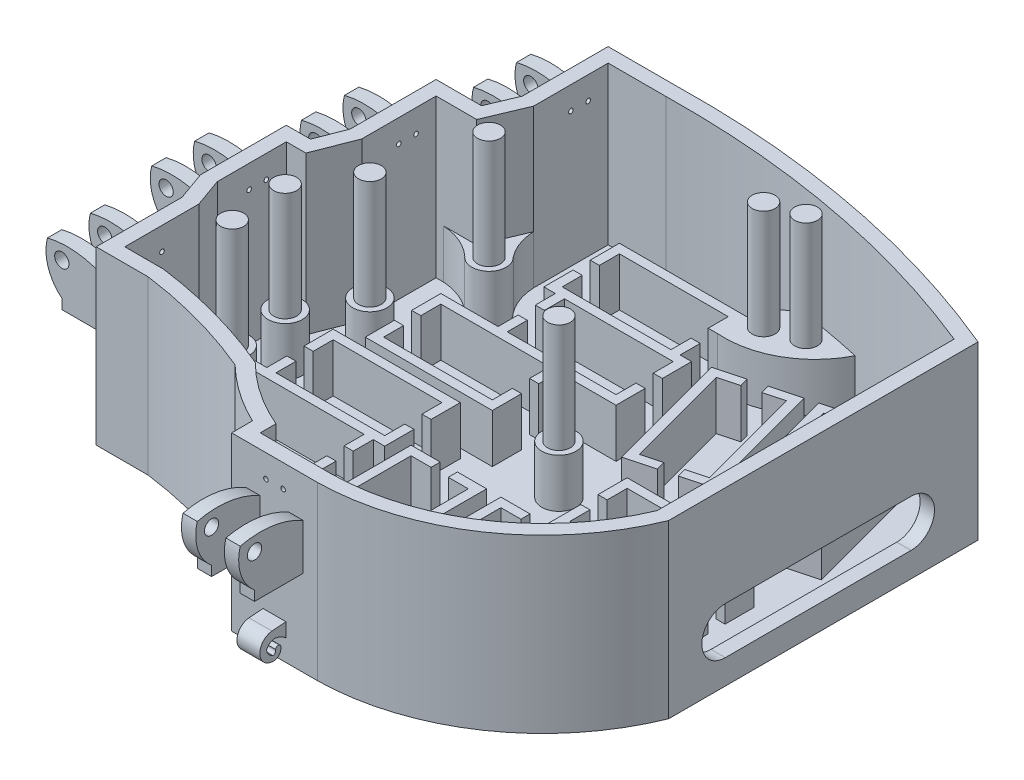
SolidWorks part; units mm, degrees
ref_plane "Front Plane" through (0, 0, 0) normal (0, 0, 1) x (1, 0, 0)
ref_plane "Top Plane" through (0, 0, 0) normal (0, 1, 0) x (1, 0, 0)
ref_plane "Right Plane" through (0, 0, 0) normal (1, 0, 0) x (0, 0, -1)
ref_plane "Palm Side Plane" through (0, 38.1, 0) normal (0, 1, 0) x (1, 0, 0)
ref_plane "Left Side Plane" through (0, 0, 63.5) normal (0, 0, 1) x (1, 0, 0)
ref_plane "Top Side Plane" through (-69.85, 0, 0) normal (1, 0, 0) x (0, 0, -1)
ref_plane "Wrist Plane" through (62.9138, 0, 0) normal (1, 0, 0) x (0, 0, -1)
sketch "Hand Direction Arrow" plane through (0, 38.1, 0) normal (0, 1, 0) x (1, 0, 0)
  line L0 (49.8191, -114.0829) -> (-36.738, -114.0829) construction
  line L1 (-36.738, -114.0829) -> (-22.4792, -131.555) construction
  line L2 (-36.738, -114.0829) -> (-22.4792, -99.8241) construction
sketch "Sketch2" plane through (0, 0, 0) normal (0, 1, 0) x (1, 0, 0)
  line L5 (-69.85, -63.5) -> (69.85, 63.5) construction
  line L6 (-69.85, 63.5) -> (69.85, -63.5) construction
  line L7 (-20.7784, 52.7587) -> (-36.189, 52.7587)
  line L8 (-36.189, 52.7587) -> (-36.189, 33.7087)
  line L9 (-42.9594, -42.4913) -> (-54.5039, -42.4913)
  line L10 (-54.5039, -42.4913) -> (-54.5039, -23.4413)
  line L11 (-54.5039, -23.4413) -> (-56.7676, -17.0913)
  line L12 (-51.4171, 1.9587) -> (-48.9477, 8.3087)
  line L14 (-56.7676, -17.0913) -> (-56.7676, 1.9587)
  line L15 (-56.7676, 1.9587) -> (-51.4171, 1.9587)
  line L16 (-38.8642, 27.3587) -> (-36.189, 33.7087)
  line L19 (15.3118, -63.2103) -> (-3.7382, -63.2103)
  line L20 (-3.7382, -63.2103) -> (-3.7382, -58.593)
  line L21 (61.5724, -31.5884) -> (61.5724, 37.0553)
  line L22 (-48.9477, 8.3087) -> (-48.9477, 27.3587)
  line L23 (-48.9477, 27.3587) -> (-38.8642, 27.3587)
  arc A0 (61.5724, 37.0553) -> (-20.7784, 52.7587) centre (-16.6219, -149.2259) ccw
  arc A2 (-42.9594, -42.4913) -> (-16.4221, -49.7553) centre (-56.8306, -145.2734) cw
  arc A5 (-3.7382, -58.593) -> (-16.4221, -49.7553) centre (16.7508, -15.6666) cw
  arc A6 (15.3118, -63.2103) -> (61.5724, -31.5884) centre (14.5642, -12.4678) ccw
  point P0 (0, 0)
  dimension "D1" = 19.05
  dimension "D2" = 19.05
  dimension "D3" = 19.05
  dimension "D4" = 19.05
  dimension "D5" = 19.05
  dimension "D6" = 6.35
  dimension "D7" = 6.35
extrude "Boss-Extrude1" add sketch "Sketch2" along normal blind 38.1
sketch "Sketch3" plane through (0, 38.1, 0) normal (0, 1, 0) x (1, 0, 0)
  line L5 (-68.58, -62.23) -> (68.58, 62.23) construction
  line L6 (-68.58, 62.23) -> (68.58, -62.23) construction
  line L7 (-20.1593, 49.595) -> (-33.014, 49.595)
  line L8 (-33.014, 49.595) -> (-33.014, 33.0672)
  line L10 (-36.189, 52.7587) -> (-36.189, 33.7087) construction
  line L11 (-54.5039, -23.4413) -> (-54.5039, -42.4913) construction
  line L12 (-42.7477, -39.3163) -> (-51.3289, -39.3163)
  line L13 (-51.3289, -39.3163) -> (-51.3289, -22.8923)
  line L18 (-53.5926, -16.5423) -> (-53.5926, -1.2163)
  line L19 (-53.5926, -1.2163) -> (-49.2452, -1.2163)
  line L22 (-56.7676, 1.9587) -> (-56.7676, -17.0913) construction
  line L23 (-51.4171, 1.9587) -> (-56.7676, 1.9587) construction
  line L24 (-45.7727, 7.713) -> (-45.7727, 24.1837)
  line L25 (-45.7727, 24.1837) -> (-36.7565, 24.1837)
  line L26 (-48.9477, 27.3587) -> (-48.9477, 8.3087) construction
  line L27 (-38.8642, 27.3587) -> (-48.9477, 27.3587) construction
  line L28 (-36.7565, 24.1837) -> (-33.014, 33.0672)
  line L29 (-36.189, 33.7087) -> (-38.8642, 27.3587) construction
  line L30 (-49.2452, -1.2163) -> (-45.7727, 7.713)
  line L31 (-54.5039, -42.4913) -> (-42.9594, -42.4913) construction
  line L32 (-51.3289, -22.8923) -> (-53.5926, -16.5423)
  line L33 (-56.7676, -17.0913) -> (-54.5039, -23.4413) construction
  line L34 (-48.9477, 8.3087) -> (-51.4171, 1.9587) construction
  line L35 (15.3312, -60.0353) -> (-0.5632, -60.0353)
  line L36 (-0.5632, -60.0353) -> (-0.5632, -56.5413)
  line L37 (-3.7382, -58.593) -> (-3.7382, -63.2103) construction
  line L38 (-3.7382, -63.2103) -> (15.3118, -63.2103) construction
  line L39 (58.3974, -30.9587) -> (58.3974, 34.9326)
  line L40 (61.5724, -31.5884) -> (61.5724, 37.0553) construction
  arc A1 (-20.1593, 49.595) -> (58.3974, 34.9326) centre (-16.6219, -149.2259) cw
  arc A4 (61.5724, 37.0553) -> (-20.7784, 52.7587) centre (-16.6219, -149.2259) ccw construction
  arc A5 (15.3118, -63.2103) -> (61.5724, -31.5884) centre (14.5642, -12.4678) ccw construction
  arc A8 (-42.7477, -39.3163) -> (-14.6223, -47.0711) centre (-56.8306, -145.2734) cw
  arc A9 (-16.4221, -49.7553) -> (-42.9594, -42.4913) centre (-56.8306, -145.2734) ccw construction
  arc A12 (15.3312, -60.0353) -> (58.3974, -30.9587) centre (14.5642, -12.4678) ccw
  arc A13 (-0.5632, -56.5413) -> (-14.6223, -47.0711) centre (16.7508, -15.6666) cw
  arc A14 (-16.4221, -49.7553) -> (-3.7382, -58.593) centre (16.7508, -15.6666) ccw construction
  point P0 (0, 0)
  point P6 (-45.5127, -25.7954)
  point P29 (-45.5127, -25.7954)
  point P52 (-54.0923, 1.9587)
  dimension "D2" = 3.175
  dimension "D3" = 3.175
  dimension "D5" = 3.175
  dimension "D6" = 3.175
  dimension "D8" = 3.175
  dimension "D4" = 3.175
  dimension "D7" = 3.175
  dimension "D9" = 3.175
  dimension "D10" = 3.175
  dimension "D11" = 3.175
  dimension "D12" = 3.175
  dimension "D13" = 3.175
  dimension "D14" = 3.175
  dimension "D15" = 3.175
  dimension "D16" = 3.175
  dimension "D17" = 3.175
extrude "Cut-Extrude1" cut sketch "Sketch3" against normal blind 34.925
sketch "Sketch6" plane through (0, 0, 0) normal (0, 1, 0) x (1, 0, 0)
  line L0 (-39.0579, -32.9145) -> (-37.0259, -32.9145)
  line L5 (-63.3937, -68.1577) -> (73.7663, 56.3023) construction
  line L6 (-64.5742, 57.9506) -> (72.5858, -66.5094) construction
  line L7 (-12.8959, -37.3595) -> (-37.0259, -37.3595)
  line L8 (-12.8959, -37.3595) -> (-12.8959, -32.9145)
  line L9 (-12.8959, -24.6595) -> (-37.0259, -24.6595)
  line L10 (-37.0259, -37.3595) -> (-37.0259, -32.9145)
  line L11 (-12.8959, -37.3595) -> (-37.0259, -24.6595) construction
  line L12 (-12.8959, -24.6595) -> (-37.0259, -37.3595) construction
  line L13 (-10.8639, -39.3915) -> (-39.0579, -39.3915)
  line L14 (-10.8639, -39.3915) -> (-10.8639, -32.9145)
  line L15 (-10.8639, -22.6275) -> (-39.0579, -22.6275)
  line L16 (-39.0579, -39.3915) -> (-39.0579, -32.9145)
  line L17 (-10.8639, -39.3915) -> (-39.0579, -22.6275) construction
  line L18 (-10.8639, -22.6275) -> (-39.0579, -39.3915) construction
  line L19 (-39.0579, -29.1045) -> (-37.0259, -29.1045)
  line L20 (-39.0579, -29.1045) -> (-39.0579, -22.6275)
  line L21 (-37.0259, -29.1045) -> (-37.0259, -24.6595)
  line L22 (-12.8959, -32.9145) -> (-10.8639, -32.9145)
  line L23 (-12.8959, -29.1045) -> (-10.8639, -29.1045)
  line L24 (-12.8959, -29.1045) -> (-12.8959, -24.6595)
  line L25 (-10.8639, -29.1045) -> (-10.8639, -22.6275)
  point P0 (5.5042, -5.6391)
  point P6 (-24.9609, -31.0095)
  point P29 (-24.9609, -31.0095)
  dimension "D6" = 2.032
  dimension "D7" = 2.032
  dimension "D9" = 12.7
  dimension "D10" = 24.13
  dimension "D11" = 4.445
  dimension "D12" = 4.445
  dimension "D13" = 4.445
  dimension "D14" = 4.445
extrude "Servo Box 1" add sketch "Sketch6" along normal blind 13.97
sketch "Sketch7" plane through (0, 0, 0) normal (0, 1, 0) x (1, 0, 0)
  line L0 (-36.5179, -18.1825) -> (-34.4859, -18.1825)
  line L5 (-10.8639, -22.6275) -> (-39.0579, -22.6275) construction
  line L7 (-10.3559, -22.6275) -> (-34.4859, -22.6275)
  line L8 (-10.3559, -22.6275) -> (-10.3559, -18.1825)
  line L9 (-10.3559, -9.9275) -> (-34.4859, -9.9275)
  line L10 (-34.4859, -22.6275) -> (-34.4859, -18.1825)
  line L11 (-10.3559, -22.6275) -> (-34.4859, -9.9275) construction
  line L12 (-10.3559, -9.9275) -> (-34.4859, -22.6275) construction
  line L13 (-8.3239, -24.6595) -> (-36.5179, -24.6595)
  line L14 (-8.3239, -24.6595) -> (-8.3239, -18.1825)
  line L15 (-8.3239, -7.8955) -> (-36.5179, -7.8955)
  line L16 (-36.5179, -24.6595) -> (-36.5179, -18.1825)
  line L17 (-8.3239, -24.6595) -> (-36.5179, -7.8955) construction
  line L18 (-8.3239, -7.8955) -> (-36.5179, -24.6595) construction
  line L19 (-36.5179, -14.3725) -> (-34.4859, -14.3725)
  line L20 (-36.5179, -14.3725) -> (-36.5179, -7.8955)
  line L21 (-34.4859, -14.3725) -> (-34.4859, -9.9275)
  line L22 (-10.3559, -18.1825) -> (-8.3239, -18.1825)
  line L23 (-10.3559, -14.3725) -> (-8.3239, -14.3725)
  line L24 (-10.3559, -14.3725) -> (-10.3559, -9.9275)
  line L25 (-8.3239, -14.3725) -> (-8.3239, -7.8955)
  line L26 (-39.0579, -22.6275) -> (-39.0579, -29.1045) construction
  point P0 (-7.5753, -5.9494)
  point P6 (-22.4209, -16.2775)
  point P29 (-22.4209, -16.2775)
  dimension "D2" = 2.032
  dimension "D3" = 2.54
  dimension "D6" = 2.032
  dimension "D7" = 2.032
  dimension "D9" = 12.7
  dimension "D10" = 24.13
  dimension "D11" = 4.445
  dimension "D12" = 4.445
  dimension "D13" = 4.445
  dimension "D14" = 4.445
extrude "Servo Box 2" add sketch "Sketch7" along normal blind 13.97
sketch "Sketch15" plane through (0, 0, 0) normal (0, -1, 0) x (1, 0, 0)
  line L0 (-31.4379, -4.4235) -> (-29.4059, -4.4235)
  line L5 (-8.3239, 7.8955) -> (-36.5179, 7.8955) construction
  line L6 (-36.5179, 7.8955) -> (-36.5179, 14.3725) construction
  line L7 (-5.2759, -8.8685) -> (-29.4059, -8.8685)
  line L8 (-5.2759, -8.8685) -> (-5.2759, -4.4235)
  line L9 (-5.2759, 3.8315) -> (-29.4059, 3.8315)
  line L10 (-29.4059, -8.8685) -> (-29.4059, -4.4235)
  line L11 (-5.2759, -8.8685) -> (-29.4059, 3.8315) construction
  line L12 (-5.2759, 3.8315) -> (-29.4059, -8.8685) construction
  line L13 (-3.2439, -10.9005) -> (-31.4379, -10.9005)
  line L14 (-3.2439, -10.9005) -> (-3.2439, -4.4235)
  line L15 (-3.2439, 5.8635) -> (-31.4379, 5.8635)
  line L16 (-31.4379, -10.9005) -> (-31.4379, -4.4235)
  line L17 (-3.2439, -10.9005) -> (-31.4379, 5.8635) construction
  line L18 (-3.2439, 5.8635) -> (-31.4379, -10.9005) construction
  line L19 (-31.4379, -0.6135) -> (-29.4059, -0.6135)
  line L20 (-31.4379, -0.6135) -> (-31.4379, 5.8635)
  line L21 (-29.4059, -0.6135) -> (-29.4059, 3.8315)
  line L22 (-5.2759, -4.4235) -> (-3.2439, -4.4235)
  line L23 (-5.2759, -0.6135) -> (-3.2439, -0.6135)
  line L24 (-5.2759, -0.6135) -> (-5.2759, 3.8315)
  line L25 (-3.2439, -0.6135) -> (-3.2439, 5.8635)
  point P0 (-6.5637, 8.998)
  point P6 (-17.3409, -2.5185)
  point P29 (-17.3409, -2.5185)
  dimension "D2" = 2.032
  dimension "D3" = 5.08
  dimension "D6" = 2.032
  dimension "D7" = 2.032
  dimension "D9" = 12.7
  dimension "D10" = 24.13
  dimension "D11" = 4.445
  dimension "D12" = 4.445
  dimension "D13" = 4.445
  dimension "D14" = 4.445
extrude "Servo Box 3" add sketch "Sketch15" against normal blind 13.97
sketch "Sketch16" plane through (0, 0, 0) normal (0, -1, 0) x (1, 0, 0)
  line L0 (-18.7379, -19.1555) -> (-16.7059, -19.1555)
  line L5 (-31.4379, -10.9005) -> (-3.2439, -10.9005) construction
  line L6 (-31.4379, -4.4235) -> (-31.4379, -10.9005) construction
  line L7 (7.4241, -23.6005) -> (-16.7059, -23.6005)
  line L8 (7.4241, -23.6005) -> (7.4241, -19.1555)
  line L9 (7.4241, -10.9005) -> (-16.7059, -10.9005)
  line L10 (-16.7059, -23.6005) -> (-16.7059, -19.1555)
  line L11 (7.4241, -23.6005) -> (-16.7059, -10.9005) construction
  line L12 (7.4241, -10.9005) -> (-16.7059, -23.6005) construction
  line L13 (9.4561, -25.6325) -> (-18.7379, -25.6325)
  line L14 (9.4561, -25.6325) -> (9.4561, -19.1555)
  line L15 (9.4561, -8.8685) -> (-18.7379, -8.8685)
  line L16 (-18.7379, -25.6325) -> (-18.7379, -19.1555)
  line L17 (9.4561, -25.6325) -> (-18.7379, -8.8685) construction
  line L18 (9.4561, -8.8685) -> (-18.7379, -25.6325) construction
  line L19 (-18.7379, -15.3455) -> (-16.7059, -15.3455)
  line L20 (-18.7379, -15.3455) -> (-18.7379, -8.8685)
  line L21 (-16.7059, -15.3455) -> (-16.7059, -10.9005)
  line L22 (7.4241, -19.1555) -> (9.4561, -19.1555)
  line L23 (7.4241, -15.3455) -> (9.4561, -15.3455)
  line L24 (7.4241, -15.3455) -> (7.4241, -10.9005)
  line L25 (9.4561, -15.3455) -> (9.4561, -8.8685)
  point P0 (1.9027, -6.9539)
  point P6 (-4.6409, -17.2505)
  point P29 (-4.6409, -17.2505)
  dimension "D2" = 2.032
  dimension "D3" = 12.7
  dimension "D6" = 2.032
  dimension "D7" = 2.032
  dimension "D9" = 12.7
  dimension "D10" = 24.13
  dimension "D11" = 4.445
  dimension "D12" = 4.445
  dimension "D13" = 4.445
  dimension "D14" = 4.445
extrude "Servo Box 4" add sketch "Sketch16" against normal blind 13.97
sketch "Sketch17" plane through (0, 0, 0) normal (0, -1, 0) x (1, 0, 0)
  line L0 (-21.2779, -33.8875) -> (-19.2459, -33.8875)
  line L5 (-18.7379, -25.6325) -> (9.4561, -25.6325) construction
  line L6 (-18.7379, -19.1555) -> (-18.7379, -25.6325) construction
  line L7 (4.8841, -38.3325) -> (-19.2459, -38.3325)
  line L8 (4.8841, -38.3325) -> (4.8841, -33.8875)
  line L9 (4.8841, -25.6325) -> (-19.2459, -25.6325)
  line L10 (-19.2459, -38.3325) -> (-19.2459, -33.8875)
  line L11 (4.8841, -38.3325) -> (-19.2459, -25.6325) construction
  line L12 (4.8841, -25.6325) -> (-19.2459, -38.3325) construction
  line L13 (6.9161, -40.3645) -> (-21.2779, -40.3645)
  line L14 (6.9161, -40.3645) -> (6.9161, -33.8875)
  line L15 (6.9161, -23.6005) -> (-21.2779, -23.6005)
  line L16 (-21.2779, -40.3645) -> (-21.2779, -33.8875)
  line L17 (6.9161, -40.3645) -> (-21.2779, -23.6005) construction
  line L18 (6.9161, -23.6005) -> (-21.2779, -40.3645) construction
  line L19 (-21.2779, -30.0775) -> (-19.2459, -30.0775)
  line L20 (-21.2779, -30.0775) -> (-21.2779, -23.6005)
  line L21 (-19.2459, -30.0775) -> (-19.2459, -25.6325)
  line L22 (4.8841, -33.8875) -> (6.9161, -33.8875)
  line L23 (4.8841, -30.0775) -> (6.9161, -30.0775)
  line L24 (4.8841, -30.0775) -> (4.8841, -25.6325)
  line L25 (6.9161, -30.0775) -> (6.9161, -23.6005)
  point P0 (6.1079, -24.4951)
  point P6 (-7.1809, -31.9825)
  point P29 (-7.1809, -31.9825)
  dimension "D2" = 2.032
  dimension "D3" = 2.54
  dimension "D6" = 2.032
  dimension "D7" = 2.032
  dimension "D9" = 12.7
  dimension "D10" = 24.13
  dimension "D11" = 4.445
  dimension "D12" = 4.445
  dimension "D13" = 4.445
  dimension "D14" = 4.445
extrude "Servo Box 5" add sketch "Sketch17" against normal blind 13.97
sketch "Sketch18" plane through (0, 0, 0) normal (0, -1, 0) x (1, 0, 0)
  line L0 (0.8802, 49.7413) -> (0.8802, 47.7093)
  line L7 (-3.5648, 23.5793) -> (-3.5648, 47.7093)
  line L8 (-3.5648, 23.5793) -> (0.8802, 23.5793)
  line L9 (9.1352, 23.5793) -> (9.1352, 47.7093)
  line L10 (-3.5648, 47.7093) -> (0.8802, 47.7093)
  line L11 (-3.5648, 23.5793) -> (9.1352, 47.7093) construction
  line L12 (9.1352, 23.5793) -> (-3.5648, 47.7093) construction
  line L13 (-5.5968, 21.5473) -> (-5.5968, 49.7413)
  line L14 (-5.5968, 21.5473) -> (0.8802, 21.5473)
  line L15 (11.1672, 21.5473) -> (11.1672, 49.7413)
  line L16 (-5.5968, 49.7413) -> (0.8802, 49.7413)
  line L17 (-5.5968, 21.5473) -> (11.1672, 49.7413) construction
  line L18 (11.1672, 21.5473) -> (-5.5968, 49.7413) construction
  line L19 (4.6902, 49.7413) -> (4.6902, 47.7093)
  line L20 (4.6902, 49.7413) -> (11.1672, 49.7413)
  line L21 (4.6902, 47.7093) -> (9.1352, 47.7093)
  line L22 (0.8802, 23.5793) -> (0.8802, 21.5473)
  line L23 (4.6902, 23.5793) -> (4.6902, 21.5473)
  line L24 (4.6902, 23.5793) -> (9.1352, 23.5793)
  line L25 (4.6902, 21.5473) -> (11.1672, 21.5473)
  point P0 (12.6654, 20.4496)
  point P6 (2.7852, 35.6443)
  point P29 (2.7852, 35.6443)
  dimension "D6" = 2.032
  dimension "D7" = 2.032
  dimension "D9" = 12.7
  dimension "D10" = 24.13
  dimension "D11" = 4.445
  dimension "D12" = 4.445
  dimension "D13" = 4.445
  dimension "D14" = 4.445
extrude "Servo Box 6" add sketch "Sketch18" against normal blind 13.97
sketch "Sketch19" plane through (0, 0, 0) normal (0, -1, 0) x (1, 0, 0)
  line L0 (20.8192, 49.7413) -> (20.8192, 47.7093)
  line L6 (11.1672, 21.5473) -> (11.1672, 49.7413) construction
  line L7 (16.3742, 23.5793) -> (16.3742, 47.7093)
  line L8 (16.3742, 23.5793) -> (20.8192, 23.5793)
  line L9 (29.0742, 23.5793) -> (29.0742, 47.7093)
  line L10 (16.3742, 47.7093) -> (20.8192, 47.7093)
  line L13 (14.3422, 21.5473) -> (14.3422, 49.7413)
  line L14 (14.3422, 21.5473) -> (20.8192, 21.5473)
  line L15 (31.1062, 21.5473) -> (31.1062, 49.7413)
  line L16 (14.3422, 49.7413) -> (20.8192, 49.7413)
  line L19 (24.6292, 49.7413) -> (24.6292, 47.7093)
  line L20 (24.6292, 49.7413) -> (31.1062, 49.7413)
  line L21 (24.6292, 47.7093) -> (29.0742, 47.7093)
  line L22 (20.8192, 23.5793) -> (20.8192, 21.5473)
  line L23 (24.6292, 23.5793) -> (24.6292, 21.5473)
  line L24 (24.6292, 23.5793) -> (29.0742, 23.5793)
  line L25 (24.6292, 21.5473) -> (31.1062, 21.5473)
  line L26 (11.1672, 49.7413) -> (4.6902, 49.7413) construction
  point P5 (0, 0)
  dimension "D2" = 0
  dimension "D3" = 2.032
  dimension "D5" = 3.175
  dimension "D6" = 2.032
  dimension "D4" = 2.032
  dimension "D7" = 2.032
  dimension "D9" = 12.7
  dimension "D10" = 24.13
  dimension "D11" = 4.445
  dimension "D12" = 4.445
  dimension "D13" = 4.445
  dimension "D14" = 4.445
extrude "Servo Box 7" add sketch "Sketch19" against normal blind 13.97
sketch "Sketch20" plane through (0, 0, 0) normal (0, -1, 0) x (1, 0, 0)
  line L0 (24.6292, 10.3085) -> (26.6612, 10.3085)
  line L7 (50.7912, 5.8635) -> (26.6612, 5.8635)
  line L8 (50.7912, 5.8635) -> (50.7912, 10.3085)
  line L9 (50.7912, 18.5635) -> (26.6612, 18.5635)
  line L10 (26.6612, 5.8635) -> (26.6612, 10.3085)
  line L13 (52.8232, 3.8315) -> (24.6292, 3.8315)
  line L14 (52.8232, 3.8315) -> (52.8232, 10.3085)
  line L15 (52.8232, 20.5955) -> (24.6292, 20.5955)
  line L16 (24.6292, 3.8315) -> (24.6292, 10.3085)
  line L19 (24.6292, 14.1185) -> (26.6612, 14.1185)
  line L20 (24.6292, 14.1185) -> (24.6292, 20.5955)
  line L21 (26.6612, 14.1185) -> (26.6612, 18.5635)
  line L22 (50.7912, 10.3085) -> (52.8232, 10.3085)
  line L23 (50.7912, 14.1185) -> (52.8232, 14.1185)
  line L24 (50.7912, 14.1185) -> (50.7912, 18.5635)
  line L25 (52.8232, 14.1185) -> (52.8232, 20.5955)
  line L26 (-3.2439, 5.8635) -> (-31.4379, 5.8635) construction
  point P3 (0, 0)
  dimension "D2" = 0
  dimension "D3" = 2.032
  dimension "D6" = 2.032
  dimension "D4" = 2.032
  dimension "D7" = 2.032
  dimension "D9" = 12.7
  dimension "D10" = 24.13
  dimension "D11" = 4.445
  dimension "D12" = 4.445
  dimension "D13" = 4.445
  dimension "D14" = 4.445
extrude "Servo Box 8" add sketch "Sketch20" against normal blind 13.97
sketch "Sketch21" plane through (0, 0, 0) normal (0, -1, 0) x (1, 0, 0)
  line L0 (22.6768, -29.4265) -> (23.2027, -27.4637)
  line L7 (33.7416, -5.3064) -> (27.4963, -28.6142)
  line L8 (33.7416, -5.3064) -> (29.448, -4.1559)
  line L9 (21.4743, -2.0194) -> (15.229, -25.3272)
  line L10 (27.4963, -28.6142) -> (23.2027, -27.4637)
  line L11 (33.7416, -5.3064) -> (15.229, -25.3272) construction
  line L12 (21.4743, -2.0194) -> (27.4963, -28.6142) construction
  line L13 (36.2303, -3.8695) -> (28.9331, -31.1029)
  line L14 (36.2303, -3.8695) -> (29.974, -2.1932)
  line L15 (20.0375, 0.4693) -> (12.7403, -26.764)
  line L16 (28.9331, -31.1029) -> (22.6768, -29.4265)
  line L17 (36.2303, -3.8695) -> (12.7403, -26.764) construction
  line L18 (20.0375, 0.4693) -> (28.9331, -31.1029) construction
  line L19 (18.9966, -28.4404) -> (19.5225, -26.4776)
  line L20 (18.9966, -28.4404) -> (12.7403, -26.764)
  line L21 (19.5225, -26.4776) -> (15.229, -25.3272)
  line L22 (29.448, -4.1559) -> (29.974, -2.1932)
  line L23 (25.7679, -3.1698) -> (26.2938, -1.2071)
  line L24 (25.7679, -3.1698) -> (21.4743, -2.0194)
  line L25 (26.2938, -1.2071) -> (20.0375, 0.4693)
  point P0 (22.3862, -0.6336)
  point P6 (24.4853, -15.3168)
  point P29 (24.4853, -15.3168)
  dimension "D6" = 2.032
  dimension "D7" = 2.032
  dimension "D9" = 12.7
  dimension "D10" = 24.13
  dimension "D11" = 4.445
  dimension "D12" = 4.445
  dimension "D13" = 4.445
  dimension "D14" = 4.445
extrude "Servo Box 9" add sketch "Sketch21" against normal blind 13.97
sketch "Sketch22" plane through (0, 0, 0) normal (0, -1, 0) x (1, 0, 0)
  line L0 (41.4457, -34.4556) -> (41.9716, -32.4928)
  line L7 (52.5105, -10.3355) -> (46.2652, -33.6433)
  line L8 (52.5105, -10.3355) -> (48.2169, -9.1851)
  line L9 (40.2432, -7.0485) -> (33.9979, -30.3563)
  line L10 (46.2652, -33.6433) -> (41.9716, -32.4928)
  line L11 (52.5105, -10.3355) -> (33.9979, -30.3563) construction
  line L12 (40.2432, -7.0485) -> (46.2652, -33.6433) construction
  line L13 (54.9992, -8.8987) -> (47.702, -36.132)
  line L14 (54.9992, -8.8987) -> (48.7429, -7.2223)
  line L15 (38.8064, -4.5598) -> (31.5092, -31.7931)
  line L16 (47.702, -36.132) -> (41.4457, -34.4556)
  line L17 (54.9992, -8.8987) -> (31.5092, -31.7931) construction
  line L18 (38.8064, -4.5598) -> (47.702, -36.132) construction
  line L19 (37.7655, -33.4695) -> (38.2915, -31.5067)
  line L20 (37.7655, -33.4695) -> (31.5092, -31.7931)
  line L21 (38.2915, -31.5067) -> (33.9979, -30.3563)
  line L22 (48.2169, -9.1851) -> (48.7429, -7.2223)
  line L23 (44.5368, -8.199) -> (45.0627, -6.2362)
  line L24 (44.5368, -8.199) -> (40.2432, -7.0485)
  line L25 (45.0627, -6.2362) -> (38.8064, -4.5598)
  line L26 (22.6768, -29.4265) -> (28.9331, -31.1029) construction
  line L27 (33.7416, -5.3064) -> (27.4963, -28.6142) construction
  point P0 (57.6091, -14.277)
  point P6 (43.2542, -20.3459)
  point P29 (43.2542, -20.3459)
  dimension "D2" = 0
  dimension "D3" = 4.699
  dimension "D6" = 2.032
  dimension "D7" = 2.032
  dimension "D9" = 12.7
  dimension "D10" = 24.13
  dimension "D11" = 4.445
  dimension "D12" = 4.445
  dimension "D13" = 4.445
  dimension "D14" = 4.445
extrude "Servo Box 10" add sketch "Sketch22" against normal blind 13.97
sketch "Sketch25" plane through (0, 0, 63.5) normal (0, 0, 1) x (1, 0, 0)
  line L0 (15.3118, 38.1) -> (15.3118, 0) construction
  line L1 (49.8191, 38.1) -> (-36.738, 38.1) construction
  line L6 (-3.7382, 38.1) -> (-3.7382, 0) construction
  circle A0 centre (7.6918, 33.02) radius 0.508
  circle A1 centre (3.8818, 33.02) radius 0.508
  dimension "D3" = 7.62
  dimension "D1" = 5.08
  dimension "D2" = 5.08
  dimension "D4" = 7.62
extrude "Thumb Holes" cut sketch "Sketch25" against normal blind 15.24
sketch "Sketch31" plane through (-69.85, 0, 0) normal (1, 0, 0) x (0, 0, -1)
  line L0 (-23.4413, 38.1) -> (-23.4413, 0) construction
  line L1 (-23.4413, 38.1) -> (-42.4913, 38.1) construction
  line L2 (-42.4913, 38.1) -> (-42.4913, 0) construction
  circle A0 centre (-31.0613, 33.02) radius 0.508
  circle A1 centre (-34.8713, 33.02) radius 0.508
  dimension "D1" = 7.62
  dimension "D2" = 5.08
  dimension "D3" = 5.08
  dimension "D4" = 7.62
extrude "Index Finger Holes" cut sketch "Sketch31" along normal blind 20.32
sketch "Sketch32" plane through (-69.85, 0, 0) normal (1, 0, 0) x (0, 0, -1)
  line L0 (1.9587, 38.1) -> (1.9587, 0) construction
  line L1 (-17.0913, 38.1) -> (-17.0913, 0) construction
  line L2 (1.9587, 38.1) -> (-17.0913, 38.1) construction
  circle A0 centre (-9.4713, 33.02) radius 0.508
  circle A1 centre (-5.6613, 33.02) radius 0.508
  dimension "D1" = 7.62
  dimension "D2" = 7.62
  dimension "D3" = 5.08
  dimension "D4" = 5.08
extrude "Middle Finger Holes" cut sketch "Sketch32" along normal blind 17.78
sketch "Sketch33" plane through (-69.85, 0, 0) normal (1, 0, 0) x (0, 0, -1)
  line L0 (27.3587, 38.1) -> (27.3587, 0) construction
  line L1 (27.3587, 38.1) -> (8.3087, 38.1) construction
  line L2 (8.3087, 38.1) -> (8.3087, 0) construction
  circle A0 centre (15.9287, 33.02) radius 0.508
  circle A1 centre (19.7387, 33.02) radius 0.508
  dimension "D1" = 7.62
  dimension "D2" = 5.08
  dimension "D3" = 5.08
  dimension "D4" = 7.62
extrude "Ring Finger Holes" cut sketch "Sketch33" along normal blind 25.4
sketch "Sketch34" plane through (-69.85, 0, 0) normal (1, 0, 0) x (0, 0, -1)
  line L0 (52.7587, 38.1) -> (33.7087, 38.1) construction
  line L1 (52.8014, 0) -> (52.8014, 38.1) construction
  line L2 (33.7087, 38.1) -> (33.7087, 0) construction
  circle A0 centre (41.3287, 33.02) radius 0.508
  circle A1 centre (45.1814, 33.02) radius 0.508
  dimension "D1" = 5.08
  dimension "D2" = 7.62
  dimension "D3" = 7.62
  dimension "D4" = 5.08
extrude "Pinky Finger Holes" cut sketch "Sketch34" along normal blind 38.1
sketch "Sketch26" plane through (0, 38.1, 0) normal (0, 1, 0) x (1, 0, 0)
  line L0 (-45.6139, -6.9195) -> (10.0481, -6.9195) construction
  line L11 (-31.4379, 0.6135) -> (-29.4059, 0.6135) construction
  circle A6 centre (17.8704, 42.6089) radius 2.54
  circle A7 centre (10.892, 40.173) radius 2.54
  circle A8 centre (-45.6139, -9.4595) radius 2.54
  circle A11 centre (-44.615, -22.1993) radius 2.54
  circle A12 centre (-38.4803, 2.201) radius 2.54
  circle A16 centre (-33.047, 23.1942) radius 2.54
  circle A25 centre (10.0481, -4.3795) radius 2.54
  dimension "D16" = 5.08
  dimension "D19" = 5.08
  dimension "D22" = 5.08
  dimension "D25" = 5.08
  dimension "D29" = 5.08
  dimension "D30" = 5.08
  dimension "D4" = 5.08
  dimension "D9" = 1.5875
extrude "Guide Poles" add sketch "Sketch26" against normal blind 36.83
sketch "Sketch68" plane through (0, 0, 0) normal (0, 1, 0) x (1, 0, 0)
  line L0 (-45.7727, 24.1837) -> (-36.7565, 24.1837)
  line L1 (-36.7565, 24.1837) -> (-33.014, 33.0672)
  line L2 (6.9161, 33.8875) -> (6.9161, 40.3645)
  line L3 (24.6292, -21.5473) -> (24.6292, -20.5955)
  line L5 (31.1062, -21.5473) -> (31.1062, -20.5955)
  line L6 (52.8232, -20.5955) -> (24.6292, -20.5955) construction
  line L7 (31.1062, -20.5955) -> (24.6292, -20.5955)
  line L8 (24.6292, -21.5473) -> (31.1062, -21.5473)
  arc A13 (-35.9681, 20.7481) -> (-30.4611, 25.9923) centre (-33.047, 23.1942) ccw
  circle A17 centre (-38.4803, 2.201) radius 3.81
  circle A18 centre (-45.6139, -9.4595) radius 3.81
  circle A21 centre (-44.615, -22.1993) radius 3.81
  arc A25 (58.3974, 34.9326) -> (-20.1593, 49.595) centre (-16.6219, -149.2259) ccw construction
  arc A26 (26.4755, 44.9) -> (13.073, 47.3967) centre (-16.6219, -149.2259) ccw
  arc A27 (58.3974, 34.9326) -> (-20.1593, 49.595) centre (-16.6219, -149.2259) ccw construction
  arc A28 (13.073, 47.3967) -> (6.9161, 40.3645) centre (14.9812, 39.5147) ccw
  arc A29 (6.9161, 33.8875) -> (26.4755, 44.9) centre (8.4764, 53.9923) ccw
  arc A30 (-30.4611, 25.9923) -> (-33.014, 33.0672) centre (-20.5306, 33.5735) cw
  arc A31 (-35.9681, 20.7481) -> (-45.7727, 24.1837) centre (-44.9447, 10.8385) ccw
  circle A32 centre (10.0481, -4.3795) radius 3.81
  dimension "D14" = 7.62
  dimension "D18" = 7.62
  dimension "D20" = 7.62
  dimension "D22" = 7.62
ref_plane "Pinky Attachment Plane" through (0, 0, -52.7587) normal (0, 0, -1) x (-1, 0, 0)
ref_plane "Ring Attachment Plane" through (0, 0, -27.3587) normal (0, 0, -1) x (-1, 0, 0)
ref_plane "Middle Attachment Plane" through (0, 0, -1.9587) normal (0, 0, -1) x (-1, 0, 0)
ref_plane "Pointer Attachment Plane" through (0, 0, 23.4413) normal (0, 0, -1) x (-1, 0, 0)
ref_plane "Thumb Attachment Plane" through (-3.7382, 0, 0) normal (-1, 0, 0) x (0, 0, 1)
sketch "Sketch35" plane through (0, 0, -52.7587) normal (0, 0, -1) x (-1, 0, 0)
  line L1 (36.189, 38.1) -> (36.189, 0) construction
  line L2 (38.8642, 38.1) -> (48.9477, 38.1) construction
  line L3 (36.189, 19.05) -> (40.634, 19.05)
  line L4 (40.634, 38.1) -> (40.634, 19.05) construction
  line L5 (36.189, 29.21) -> (36.189, 19.05)
  line L6 (36.189, 38.1) -> (36.189, 0) construction
  line L7 (40.634, 19.05) -> (46.984, 19.05)
  line L9 (46.984, 19.05) -> (46.984, 21.2492)
  circle A1 centre (46.984, 28.575) radius 1.5875
  arc A2 (50.159, 31.242) -> (46.984, 21.2492) centre (40.8478, 28.6996) cw
  arc A3 (50.159, 31.242) -> (36.189, 29.21) centre (45.7208, 12.7162) ccw
  dimension "D1" = 10.795
  dimension "D2" = 4.445
  dimension "D3" = 8.89
  dimension "D6" = 10.795
  dimension "D4" = 6.858
  dimension "D5" = 13.97
extrude "Pinky Attachment" add sketch "Sketch35" against normal blind 19.05
sketch "Sketch36" plane through (0, 0, -27.3587) normal (0, 0, -1) x (-1, 0, 0)
  line L0 (51.4171, 38.1) -> (56.7676, 38.1) construction
  line L3 (48.9477, 29.21) -> (48.9477, 19.05)
  line L4 (48.9477, 38.1) -> (48.9477, 0) construction
  line L5 (48.9477, 19.05) -> (53.3927, 19.05)
  line L6 (53.3927, 38.1) -> (53.3927, 19.05) construction
  line L7 (48.9477, 38.1) -> (48.9477, 0) construction
  line L8 (53.3927, 19.05) -> (59.7427, 19.05)
  line L9 (59.7427, 19.05) -> (59.7427, 21.2492)
  arc A0 (62.9177, 31.242) -> (59.7427, 21.2492) centre (53.6065, 28.6996) cw
  circle A1 centre (59.7427, 28.7074) radius 1.5875
  arc A2 (48.9477, 29.21) -> (62.9177, 31.242) centre (58.4796, 12.7162) cw
  dimension "D1" = 4.445
  dimension "D2" = 10.795
  dimension "D3" = 13.97
  dimension "D5" = 10.795
  dimension "D4" = 6.858
extrude "Ring Attachment" add sketch "Sketch36" against normal blind 19.05
sketch "Sketch37" plane through (0, 0, -1.9587) normal (0, 0, -1) x (-1, 0, 0)
  line L0 (51.4171, 38.1) -> (56.7676, 38.1) construction
  line L2 (56.7676, 29.21) -> (56.7676, 19.05)
  line L3 (56.7676, 38.1) -> (56.7676, 0) construction
  line L4 (56.7676, 19.05) -> (61.2126, 19.05)
  line L7 (61.2126, 38.1) -> (61.2126, 19.05) construction
  line L8 (61.2126, 19.05) -> (67.5626, 19.05)
  line L9 (67.5626, 19.05) -> (67.5626, 21.2492)
  arc A2 (70.7376, 31.242) -> (67.5626, 21.2492) centre (61.4264, 28.6996) cw
  circle A3 centre (67.5626, 28.575) radius 1.5875
  arc A4 (56.7676, 29.21) -> (70.7376, 31.242) centre (66.2994, 12.7162) cw
  dimension "D1" = 4.445
  dimension "D4" = 10.795
  dimension "D3" = 13.97
  dimension "D2" = 10.795
  dimension "D5" = 6.858
extrude "Middle Attachment" add sketch "Sketch37" against normal blind 19.05
sketch "Sketch38" plane through (0, 0, 23.4413) normal (0, 0, -1) x (-1, 0, 0)
  line L0 (51.4171, 38.1) -> (56.7676, 38.1) construction
  line L3 (58.9489, 38.1) -> (58.9489, 19.05) construction
  line L5 (54.5039, 38.1) -> (54.5039, 0) construction
  line L6 (54.5039, 38.1) -> (54.5039, 0) construction
  line L7 (54.5039, 29.21) -> (54.5039, 19.05)
  line L9 (56.7676, 19.05) -> (67.5626, 19.05) construction
  line L10 (65.2989, 19.05) -> (65.2989, 21.2492)
  line L11 (65.2989, 19.05) -> (54.5039, 19.05)
  arc A2 (68.4739, 31.242) -> (65.2989, 21.2492) centre (59.1628, 28.6996) cw
  circle A3 centre (65.2989, 28.575) radius 1.5875
  arc A4 (54.5039, 29.21) -> (68.4739, 31.242) centre (64.0358, 12.7162) cw
  dimension "D3" = 13.97
  dimension "D1" = 4.445
  dimension "D5" = 10.795
  dimension "D2" = 10.795
  dimension "D4" = 6.858
extrude "Pointer Attachment" add sketch "Sketch38" against normal blind 19.05
sketch "Sketch39" plane through (-3.7382, 0, 0) normal (-1, 0, 0) x (0, 0, 1)
  line L0 (63.2103, 38.1) -> (63.2103, 0) construction
  line L4 (63.2103, 19.05) -> (67.6553, 19.05)
  line L6 (63.2103, 29.21) -> (63.2103, 19.05)
  line L7 (67.6553, 38.1) -> (67.6553, 19.05) construction
  line L8 (67.6553, 19.05) -> (74.0053, 19.05)
  line L9 (74.0053, 19.05) -> (74.0053, 21.2492)
  arc A0 (77.1803, 31.242) -> (74.0053, 21.2492) centre (67.8692, 28.6996) cw
  circle A1 centre (74.0053, 28.575) radius 1.5875
  arc A2 (63.2103, 29.21) -> (77.1803, 31.242) centre (72.7422, 12.7162) cw
  dimension "D1" = 4.445
  dimension "D3" = 13.97
  dimension "D5" = 10.795
  dimension "D2" = 10.795
  dimension "D4" = 6.858
extrude "Thumb Attachment" add sketch "Sketch39" against normal blind 19.05
sketch "Sketch40" plane through (0, 38.1, 0) normal (0, 1, 0) x (1, 0, 0)
  line L0 (-56.7676, 1.9587) -> (-56.7676, -17.0913) construction
  line L1 (2.6118, -63.2103) -> (8.9618, -63.2103)
  line L2 (2.6118, -63.2103) -> (2.6118, -80.1392)
  line L4 (8.9618, -63.2103) -> (8.9618, -80.1964)
  line L5 (-0.5632, -63.2103) -> (-0.5632, -80.1392)
  line L6 (-0.5632, -80.1392) -> (2.6118, -80.1392)
  line L7 (-6.4204, -63.2103) -> (-0.5632, -63.2103)
  line L8 (15.3118, -63.2103) -> (12.1368, -63.2103)
  line L9 (12.1368, -63.2103) -> (12.1368, -80.1964)
  line L10 (12.1368, -80.1964) -> (8.9618, -80.1964)
  line L11 (-54.5039, -42.4913) -> (-54.5039, -39.3163)
  line L13 (-54.5039, -39.3163) -> (-69.4507, -39.3163)
  line L15 (-69.4507, -39.3163) -> (-69.4507, -36.1413)
  line L16 (-69.4507, -36.1413) -> (-54.5039, -36.1413)
  line L17 (-54.5039, -36.1413) -> (-54.5039, -29.7913)
  line L18 (-54.5039, -29.7913) -> (-69.5228, -29.7913)
  line L19 (-69.5228, -29.7913) -> (-69.5228, -26.6163)
  line L20 (-69.5228, -26.6163) -> (-54.5039, -26.6163)
  line L21 (-54.5039, -26.6163) -> (-54.5039, -23.4413)
  line L22 (-56.7676, -17.0913) -> (-56.7676, -13.9163)
  line L24 (-56.7676, -13.9163) -> (-71.425, -13.9163)
  line L25 (-71.425, -13.9163) -> (-71.425, -10.7413)
  line L26 (-71.425, -10.7413) -> (-56.7676, -10.7413)
  line L27 (-56.7676, -10.7413) -> (-56.7676, -4.3913)
  line L28 (-56.7676, -4.3913) -> (-71.3004, -4.3913)
  line L29 (-71.3004, -4.3913) -> (-71.3004, -1.2163)
  line L31 (-56.7676, -1.2163) -> (-56.7676, 1.9587)
  line L32 (-71.3004, -1.2163) -> (-56.7676, -1.2163)
  line L33 (-45.7727, 24.1837) -> (-45.7727, 7.713) construction
  line L34 (-48.9477, 8.3087) -> (-48.9477, 11.4837)
  line L36 (-48.9477, 11.4837) -> (-65.3617, 11.4837)
  line L37 (-65.3617, 11.4837) -> (-65.3617, 14.6587)
  line L38 (-65.3617, 14.6587) -> (-48.9477, 14.6587)
  line L39 (-48.9477, 14.6587) -> (-48.9477, 21.0087)
  line L40 (-48.9477, 21.0087) -> (-65.7763, 21.0087)
  line L41 (-65.7763, 21.0087) -> (-65.7763, 24.1837)
  line L42 (-65.7763, 24.1837) -> (-48.9477, 24.1837)
  line L43 (-48.9477, 24.1837) -> (-48.9477, 27.3587)
  line L44 (-36.189, 33.7087) -> (-36.189, 36.8837)
  line L45 (-0.5632, -60.0353) -> (15.3312, -60.0353) construction
  line L46 (-36.189, 36.8837) -> (-51.8787, 36.8837)
  line L47 (-51.8787, 36.8837) -> (-51.8787, 40.0587)
  line L48 (-51.8787, 40.0587) -> (-36.189, 40.0587)
  line L49 (-36.189, 40.0587) -> (-36.189, 46.4087)
  line L50 (-36.189, 46.4087) -> (-51.7392, 46.4087)
  line L51 (-51.7392, 46.4087) -> (-51.7392, 49.5837)
  line L52 (-51.7392, 49.5837) -> (-36.189, 49.5837)
  line L53 (-36.189, 49.5837) -> (-36.189, 52.7587)
  line L54 (15.3118, -63.2103) -> (-3.7382, -63.2103) construction
  line L55 (-48.9477, 27.3587) -> (-48.9477, 8.3087) construction
  line L56 (-0.5632, -60.0353) -> (15.3312, -60.0353) construction
  line L57 (-3.7382, -63.2103) -> (-3.7382, -77.1803) construction
  line L58 (15.3118, -77.1803) -> (15.3118, -63.2103) construction
  line L60 (-56.7676, -17.0913) -> (-56.7676, 1.9587) construction
  arc A0 (-6.4204, -63.2103) -> (15.3118, -63.2103) centre (4.4457, -71.7068) ccw
  arc A1 (-54.5039, -42.4913) -> (-54.5039, -23.4413) centre (-62.4336, -32.9663) cw
  arc A2 (-56.7676, -17.0913) -> (-56.7676, 1.9587) centre (-65.4831, -7.5663) cw
  arc A4 (-36.189, 33.7087) -> (-36.189, 52.7587) centre (-43.6792, 43.2337) cw
  arc A5 (-48.9477, 8.3087) -> (-48.9477, 27.3587) centre (-56.9849, 17.8337) cw
  dimension "D1" = 3.175
  dimension "D2" = 3.175
  dimension "D3" = 3.175
  dimension "D4" = 3.175
  dimension "D5" = 3.175
  dimension "D6" = 3.175
  dimension "D7" = 3.175
  dimension "D8" = 3.175
  dimension "D9" = 3.175
  dimension "D10" = 3.175
  dimension "D11" = 3.175
  dimension "D12" = 3.175
  dimension "D13" = 3.175
  dimension "D14" = 3.175
  dimension "D15" = 3.175
  dimension "D17" = 3.175
  dimension "D19" = 3.175
  dimension "D20" = 3.175
  dimension "D22" = 3.175
  dimension "D24" = 3.175
  dimension "D25" = 3.175
  dimension "D26" = 3.175
  dimension "D27" = 3.175
  dimension "D28" = 3.175
extrude "Attachment Trim" cut sketch "Sketch40" against normal blind 25.4
sketch "Sketch41" plane through (62.9138, 0, 0) normal (1, 0, 0) x (0, 0, -1)
  line L0 (-19.0129, 10.6596) -> (22.2009, 10.6596) construction
  line L1 (-19.0129, 15.8519) -> (22.2009, 15.8519)
  line L2 (-19.0129, 5.4674) -> (22.2009, 5.4674)
  arc A0 (-19.0129, 15.8519) -> (-19.0129, 5.4674) centre (-19.0129, 10.6596) ccw
  arc A1 (22.2009, 5.4674) -> (22.2009, 15.8519) centre (22.2009, 10.6596) ccw
  point P2 (1.594, 10.6596)
extrude "Cord Hole" cut sketch "Sketch41" against normal blind 5.08
sketch "Band Reference Line (Fingers)" plane through (0, 0, 0) normal (0, 0, 1) x (1, 0, 0)
  line L0 (-36.189, 8.89) -> (-63.3567, 8.89) construction
  line L1 (-36.189, 38.1) -> (-36.189, 0) construction
  line L2 (-38.8642, 0) -> (-48.9477, 0) construction
  dimension "D1" = 8.89
sketch "Sketch46" plane through (0, 0, -52.7587) normal (0, 0, -1) x (-1, 0, 0)
  line L0 (36.189, 7.8444) -> (58.9024, 7.8444) construction
  line L1 (36.189, 38.1) -> (36.189, 0) construction
  line L10 (39.3207, 7.6215) -> (36.189, 7.8444)
  line L11 (36.189, 7.8444) -> (36.189, 4.7274)
  arc A18 (38.8033, 5.908) -> (36.189, 4.7274) centre (39.1838, 1.5806) ccw
  arc A19 (40.5007, 4.5389) -> (38.8033, 5.908) centre (38.4739, 3.7629) ccw
  arc A20 (39.1168, 2.809) -> (40.5007, 4.5389) centre (38.379, 4.8177) ccw
  arc A21 (38.5219, 3.7062) -> (39.1168, 2.809) centre (39.1178, 3.4555) ccw
  arc A22 (37.3157, 3.4012) -> (38.5219, 3.7062) centre (37.9188, 3.5537) cw
  arc A23 (38.9608, 1.6579) -> (37.3157, 3.4012) centre (38.9609, 3.3059) cw
  arc A24 (41.9584, 5.1066) -> (39.3207, 7.6215) centre (39.0034, 4.648) ccw
  arc A25 (38.9608, 1.6579) -> (41.9584, 5.1066) centre (39.0034, 4.648) ccw
extrude "Pinky Hook" add sketch "Sketch46" against normal blind 19.05
sketch "Sketch52" plane through (0, 0, -27.3587) normal (0, 0, -1) x (-1, 0, 0)
  line L0 (48.9477, 7.8444) -> (71.6611, 7.8444) construction
  line L1 (52.0794, 7.6215) -> (48.9477, 7.8444)
  line L2 (48.9477, 7.8444) -> (48.9477, 4.7274)
  arc A18 (51.562, 5.908) -> (48.9477, 4.7274) centre (51.9425, 1.5806) ccw
  arc A19 (53.2594, 4.5389) -> (51.562, 5.908) centre (51.2326, 3.7629) ccw
  arc A20 (51.8755, 2.809) -> (53.2594, 4.5389) centre (51.1377, 4.8177) ccw
  arc A21 (51.2806, 3.7062) -> (51.8755, 2.809) centre (51.8765, 3.4555) ccw
  arc A22 (50.0744, 3.4012) -> (51.2806, 3.7062) centre (50.6775, 3.5537) cw
  arc A23 (51.7195, 1.6579) -> (50.0744, 3.4012) centre (51.7196, 3.3059) cw
  arc A24 (54.7171, 5.1066) -> (52.0794, 7.6215) centre (51.7621, 4.648) ccw
  arc A25 (51.7195, 1.6579) -> (54.7171, 5.1066) centre (51.7621, 4.648) ccw
extrude "Ring Hook" add sketch "Sketch52" against normal blind 19.05
sketch "Sketch56" plane through (0, 0, -1.9587) normal (0, 0, -1) x (-1, 0, 0)
  line L0 (56.7676, 7.8444) -> (79.481, 7.8444) construction
  line L1 (59.8993, 7.6215) -> (56.7676, 7.8444)
  line L2 (56.7676, 7.8444) -> (56.7676, 4.7274)
  line L9 (56.7676, 38.1) -> (56.7676, 0) construction
  arc A18 (59.3819, 5.908) -> (56.7676, 4.7274) centre (59.7624, 1.5806) ccw
  arc A19 (61.0793, 4.5389) -> (59.3819, 5.908) centre (59.0525, 3.7629) ccw
  arc A20 (59.6954, 2.809) -> (61.0793, 4.5389) centre (58.9576, 4.8177) ccw
  arc A21 (59.1005, 3.7062) -> (59.6954, 2.809) centre (59.6964, 3.4555) ccw
  arc A22 (57.8943, 3.4012) -> (59.1005, 3.7062) centre (58.4974, 3.5537) cw
  arc A23 (59.5394, 1.6579) -> (57.8943, 3.4012) centre (59.5395, 3.3059) cw
  arc A24 (62.537, 5.1066) -> (59.8993, 7.6215) centre (59.582, 4.648) ccw
  arc A25 (59.5394, 1.6579) -> (62.537, 5.1066) centre (59.582, 4.648) ccw
  point P19 (0, 0)
  point P22 (0, 0)
extrude "Middle Hook" add sketch "Sketch56" against normal blind 19.05 separate body
sketch "Sketch59" plane through (0, 0, 23.4413) normal (0, 0, -1) x (-1, 0, 0)
  line L0 (54.5039, 7.8444) -> (77.2173, 7.8444) construction
  line L1 (57.6356, 7.6215) -> (54.5039, 7.8444)
  line L2 (54.5039, 7.8444) -> (54.5039, 4.7274)
  arc A18 (57.1182, 5.908) -> (54.5039, 4.7274) centre (57.4988, 1.5806) ccw
  arc A19 (58.8156, 4.5389) -> (57.1182, 5.908) centre (56.7889, 3.7629) ccw
  arc A20 (57.4317, 2.809) -> (58.8156, 4.5389) centre (56.6939, 4.8177) ccw
  arc A21 (56.8369, 3.7062) -> (57.4317, 2.809) centre (57.4327, 3.4555) ccw
  arc A22 (55.6307, 3.4012) -> (56.8369, 3.7062) centre (56.2338, 3.5537) cw
  arc A23 (57.2757, 1.6579) -> (55.6307, 3.4012) centre (57.2759, 3.3059) cw
  arc A24 (60.2733, 5.1066) -> (57.6356, 7.6215) centre (57.3184, 4.648) ccw
  arc A25 (57.2757, 1.6579) -> (60.2733, 5.1066) centre (57.3184, 4.648) ccw
extrude "Pointer Hook" add sketch "Sketch59" against normal blind 19.05
sketch "Band Reference Line (Thumb)" plane through (-3.7382, 0, 0) normal (-1, 0, 0) x (0, 0, 1)
  line L0 (58.593, 8.89) -> (76.2209, 8.89) construction
  line L1 (58.593, 38.1) -> (58.593, 0) construction
  line L2 (58.593, 0) -> (63.2103, 0) construction
  dimension "D1" = 8.89
sketch "Sketch63" plane through (-3.7382, 0, 0) normal (-1, 0, 0) x (0, 0, 1)
  line L0 (63.2103, 7.8444) -> (85.9238, 7.8444) construction
  line L1 (66.3421, 7.6215) -> (63.2103, 7.8444)
  line L2 (63.2103, 7.8444) -> (63.2103, 4.7274)
  arc A18 (65.8247, 5.908) -> (63.2103, 4.7274) centre (66.2052, 1.5806) ccw
  arc A19 (67.522, 4.5389) -> (65.8247, 5.908) centre (65.4953, 3.7629) ccw
  arc A20 (66.1381, 2.809) -> (67.522, 4.5389) centre (65.4003, 4.8177) ccw
  arc A21 (65.5433, 3.7062) -> (66.1381, 2.809) centre (66.1392, 3.4555) ccw
  arc A22 (64.3371, 3.4012) -> (65.5433, 3.7062) centre (64.9402, 3.5537) cw
  arc A23 (65.9821, 1.6579) -> (64.3371, 3.4012) centre (65.9823, 3.3059) cw
  arc A24 (68.9798, 5.1066) -> (66.3421, 7.6215) centre (66.0248, 4.648) ccw
  arc A25 (65.9821, 1.6579) -> (68.9798, 5.1066) centre (66.0248, 4.648) ccw
extrude "Thumb Hook" add sketch "Sketch63" against normal blind 19.05
sketch "Sketch65" plane through (0, 0, 0) normal (0, 1, 0) x (1, 0, 0)
  line L1 (-3.9324, -74.9448) -> (3.2468, -74.9448)
  line L2 (-3.9324, -74.9448) -> (-3.9324, -63.2103)
  line L3 (-3.9324, -63.2103) -> (3.2468, -63.2103)
  line L4 (3.2468, -74.9448) -> (3.2468, -63.2103)
  line L5 (-54.5039, -23.4413) -> (-54.5039, -42.4913) construction
  line L6 (8.3268, -77.354) -> (15.3118, -77.354)
  line L7 (8.3268, -77.354) -> (8.3268, -63.2103)
  line L8 (8.3268, -63.2103) -> (15.3118, -63.2103)
  line L9 (15.3118, -77.354) -> (15.3118, -63.2103)
  line L10 (-63.1106, -42.4913) -> (-54.5039, -42.4913)
  line L11 (-63.1106, -42.4913) -> (-63.1106, -35.5063)
  line L12 (-63.1106, -35.5063) -> (-54.5039, -35.5063)
  line L13 (-54.5039, -42.4913) -> (-54.5039, -35.5063)
  line L15 (-54.5039, -23.4413) -> (-63.5828, -23.4413)
  line L16 (-54.5039, -23.4413) -> (-54.5039, -30.4263)
  line L17 (-54.5039, -30.4263) -> (-63.5828, -30.4263)
  line L18 (-63.5828, -23.4413) -> (-63.5828, -30.4263)
  line L31 (-48.9477, 27.3587) -> (-58.251, 27.3587)
  line L32 (-48.9477, 27.3587) -> (-48.9477, 20.3737)
  line L33 (-48.9477, 20.3737) -> (-58.251, 20.3737)
  line L34 (-58.251, 27.3587) -> (-58.251, 20.3737)
  line L36 (-48.9477, 15.2937) -> (-57.3242, 15.2937)
  line L37 (-48.9477, 15.2937) -> (-48.9477, 8.3087)
  line L38 (-48.9477, 8.3087) -> (-57.3242, 8.3087)
  line L39 (-57.3242, 15.2937) -> (-57.3242, 8.3087)
  line L42 (-36.189, 52.7587) -> (-45.9243, 52.7587)
  line L43 (-36.189, 52.7587) -> (-36.189, 45.7737)
  line L44 (-36.189, 45.7737) -> (-45.9243, 45.7737)
  line L45 (-45.9243, 52.7587) -> (-45.9243, 45.7737)
  line L47 (-36.189, 33.7087) -> (-45.3683, 33.7087)
  line L48 (-36.189, 33.7087) -> (-36.189, 40.6937)
  line L49 (-36.189, 40.6937) -> (-45.3683, 40.6937)
  line L50 (-45.3683, 33.7087) -> (-45.3683, 40.6937)
  line L51 (-56.7676, 1.9587) -> (-66.1154, 1.9587)
  line L52 (-56.7676, 1.9587) -> (-56.7676, -5.0263)
  line L53 (-56.7676, -5.0263) -> (-66.1154, -5.0263)
  line L54 (-66.1154, 1.9587) -> (-66.1154, -5.0263)
  line L55 (-66.1154, -10.1063) -> (-56.7676, -10.1063)
  line L56 (-66.1154, -10.1063) -> (-66.1154, -17.0913)
  line L57 (-66.1154, -17.0913) -> (-56.7676, -17.0913)
  line L58 (-56.7676, -10.1063) -> (-56.7676, -17.0913)
  dimension "D1" = 5.08
  dimension "D2" = 6.985
  dimension "D3" = 5.08
  dimension "D4" = 6.985
  dimension "D5" = 6.985
  dimension "D6" = 5.08
  dimension "D7" = 5.08
  dimension "D8" = 6.985
  dimension "D9" = 5.08
  dimension "D10" = 6.985
extrude "Cut-Extrude9" cut sketch "Sketch65" along normal blind 13.97
sketch "Sketch67" plane through (0, 0, 0) normal (0, 1, 0) x (1, 0, 0)
  line L1 (-56.7676, -17.0913) -> (-63.2953, -17.0913)
  line L2 (-56.7676, -17.0913) -> (-56.7676, -10.1063)
  line L3 (-56.7676, -10.1063) -> (-63.2953, -10.1063)
  line L4 (-63.2953, -17.0913) -> (-63.2953, -10.1063)
  line L5 (-63.2953, -5.0263) -> (-56.7676, -5.0263)
  line L6 (-63.2953, -5.0263) -> (-63.2953, 1.9587)
  line L7 (-63.2953, 1.9587) -> (-56.7676, 1.9587)
  line L8 (-56.7676, -5.0263) -> (-56.7676, 1.9587)
  dimension "D1" = 5.08
  dimension "D2" = 6.985
extrude "Cut-Extrude10" cut sketch "Sketch67" along normal blind 12.7
extrude "Boss-Extrude2" add sketch "Sketch68" along normal blind 13.97 contours A31 A13 A30 L1 L0 | L2 A29 A26 A28 | A21 | A18 | A17 | L1 A30 A13 A31 L0 | A32 | L7 L3 L8 L5 region at (-33.7484, 0, -24.2894) region at (15.0256, 0, -40.9215)
